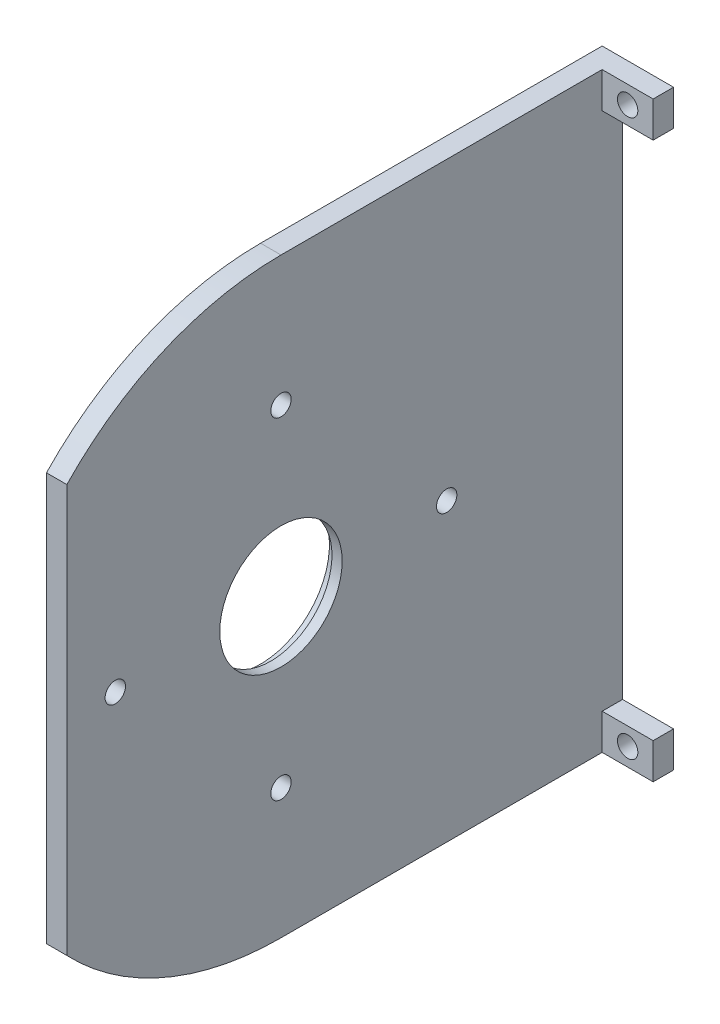
SolidWorks part; units mm, degrees
ref_plane "Front Plane" through (0, 0, 0) normal (0, 0, 1) x (1, 0, 0)
ref_plane "Top Plane" through (0, 0, 0) normal (0, 1, 0) x (1, 0, 0)
ref_plane "Right Plane" through (0, 0, 0) normal (1, 0, 0) x (0, 0, -1)
sketch "Sketch1" plane through (0, 0, 0) normal (1, 0, 0) x (0, 0, -1)
  line L0 (62.5, 58) -> (-4.5, 58)
  line L1 (-62.5, -58) -> (62.5, -58) construction
  line L2 (-62.5, -58) -> (-62.5, 58) construction
  line L3 (-62.5, 58) -> (62.5, 58) construction
  line L4 (62.5, -58) -> (62.5, 58) construction
  line L5 (-62.5, -58) -> (62.5, 58) construction
  line L6 (-62.5, 58) -> (62.5, -58) construction
  line L7 (62.5, -58) -> (-4.5, -58)
  line L8 (62.5, -58) -> (62.5, 58)
  arc A0 (-4.5, 58) -> (-4.5, -58) centre (-4.5, 0) ccw
  circle A2 centre (-4.5, 0) radius 12
  point P0 (0, 0)
  dimension "D3" = 116
  dimension "D4" = 24
  dimension "D1" = 125
  dimension "D2" = 116
extrude "Boss-Extrude1" add sketch "Sketch1" along normal blind 4
sketch "Sketch2" [suppressed] plane through (4, 0, 0) normal (1, 0, 0) x (0, 0, -1)
  circle A0 centre (-4.5, 0) radius 13.5
  circle A1 centre (-4.5, 0) radius 12 construction
  dimension "D1" = 27
extrude "Cut-Extrude1" [suppressed] cut sketch "Sketch2" against normal blind 2
sketch "Sketch4" plane through (0, 0, 0) normal (-1, 0, 0) x (0, 0, 1)
  circle A0 centre (4.5, 0) radius 13.5
  circle A1 centre (4.5, 0) radius 12 construction
  dimension "D1" = 27
extrude "Cut-Extrude2" cut sketch "Sketch4" against normal blind 2
sketch "Sketch5" [suppressed] plane through (0, 0, -62.5) normal (0, 0, -1) x (-1, 0, 0)
  line L0 (-4, -58) -> (-4, 58) construction
  line L1 (-4, 58) -> (-14, 58)
  line L2 (-4, 58) -> (-4, 51)
  line L3 (-4, 51) -> (-14, 51)
  line L4 (-14, 58) -> (-14, 51)
  line L5 (-4, 54.5) -> (-9, 54.5) construction
  line L6 (-4, 58) -> (0, 58) construction
  line L7 (0, 0) -> (12.1764, 0) construction
  line L8 (-4, -51) -> (-14, -51)
  line L9 (-14, -58) -> (-14, -51)
  line L10 (-4, -58) -> (-14, -58)
  line L11 (-4, -58) -> (-4, -51)
  line L12 (-2, 58) -> (-2, 71.3706) construction
  line L13 (0, -58) -> (0, -51)
  line L14 (0, -58) -> (10, -58)
  line L15 (10, -58) -> (10, -51)
  line L16 (0, -51) -> (10, -51)
  line L17 (0, 51) -> (10, 51) construction
  line L18 (10, 58) -> (10, 51) construction
  line L19 (0, 58) -> (10, 58) construction
  line L20 (0, 58) -> (0, 51) construction
  circle A0 centre (-9, 54.5) radius 2
  circle A1 centre (-9, -54.5) radius 2
  circle A2 centre (5, -54.5) radius 2
  circle A3 centre (5, 54.5) radius 2 construction
  dimension "D1" = 4
  dimension "D2" = 5
  dimension "D3" = 10
  dimension "D5" = 7
  dimension "D4" = 3.5
extrude "Boss-Extrude2" [suppressed] add sketch "Sketch5" against normal blind 4
sketch "Sketch6" plane through (0, 0, -62.5) normal (0, 0, -1) x (-1, 0, 0)
  line L0 (-4, -58) -> (-4, 58) construction
  line L1 (-4, 58) -> (-14, 58)
  line L2 (-4, 58) -> (-4, 51)
  line L3 (-4, 51) -> (-14, 51)
  line L4 (-14, 58) -> (-14, 51)
  line L5 (-4, 54.5) -> (-9, 54.5) construction
  line L6 (-2, -58) -> (-2, 0) construction
  line L7 (0, 0) -> (26.903, 0) construction
  line L8 (-4, -51) -> (-14, -51)
  line L9 (-14, -58) -> (-14, -51)
  line L10 (-4, -58) -> (-14, -58)
  line L11 (-4, -58) -> (-4, -51)
  line L12 (-4, 58) -> (0, 58) construction
  line L13 (-4, -58) -> (0, -58) construction
  line L14 (0, 51) -> (10, 51) construction
  line L15 (10, 58) -> (10, 51) construction
  line L16 (0, 58) -> (10, 58) construction
  line L17 (0, 58) -> (0, 51) construction
  line L18 (0, -58) -> (0, -51) construction
  line L19 (0, -58) -> (10, -58) construction
  line L20 (10, -58) -> (10, -51) construction
  line L21 (0, -51) -> (10, -51) construction
  circle A0 centre (-9, 54.5) radius 2
  circle A1 centre (-9, -54.5) radius 2
  circle A2 centre (5, -54.5) radius 2 construction
  circle A3 centre (5, 54.5) radius 2 construction
  dimension "D1" = 4
  dimension "D2" = 5
  dimension "D3" = 10
  dimension "D4" = 7
  dimension "D5" = 3.5
extrude "Boss-Extrude3" add sketch "Sketch6" against normal blind 4
sketch "Sketch7" [suppressed] plane through (0, 0, -62.5) normal (0, 0, -1) x (-1, 0, 0)
  line L0 (0, -58) -> (0, 58) construction
  line L1 (0, 58) -> (10, 58)
  line L2 (0, 58) -> (0, 51)
  line L3 (0, 51) -> (10, 51)
  line L4 (10, 58) -> (10, 51)
  line L5 (0, 0) -> (11.9371, 0) construction
  line L6 (0, -51) -> (10, -51)
  line L7 (10, -58) -> (10, -51)
  line L8 (0, -58) -> (10, -58)
  line L9 (0, -58) -> (0, -51)
  circle A0 centre (5, 54.5) radius 2
  circle A1 centre (5, -54.5) radius 2
  dimension "D5" = 3.5
  dimension "D3" = 4
  dimension "D1" = 10
  dimension "D2" = 7
  dimension "D4" = 5
extrude "Boss-Extrude4" [suppressed] add sketch "Sketch7" along normal blind 4 separate body
sketch "Sketch8" [suppressed] plane through (0, 0, 0) normal (-1, 0, 0) x (0, 0, 1)
  circle A0 centre (4.5, 0) radius 20
  dimension "D1" = 40
extrude "Cut-Extrude3" [suppressed] cut sketch "Sketch8" against normal through all
sketch "Sketch9" plane through (4, 0, 0) normal (1, 0, 0) x (0, 0, -1)
  line L0 (-46.5, 40) -> (-46.5, -40)
  arc A0 (-4.5, 58) -> (-4.5, -58) centre (-4.5, 0) ccw construction
  arc A1 (-46.5, 40) -> (-46.5, -40) centre (-4.5, 0) ccw
  dimension "D1" = 80
extrude "Cut-Extrude4" cut sketch "Sketch9" against normal through all
sketch "Sketch10" [suppressed] plane through (0, 0, 0) normal (-1, 0, 0) x (0, 0, 1)
  circle A0 centre (4.5, 0) radius 27.5
  dimension "D1" = 55
extrude "Cut-Extrude5" [suppressed] cut sketch "Sketch10" against normal through all
sketch "Sketch11" [suppressed] plane through (0, 0, 0) normal (-1, 0, 0) x (0, 0, 1)
  circle A0 centre (4.5, 0) radius 29
  dimension "D1" = 58
extrude "Cut-Extrude6" [suppressed] cut sketch "Sketch11" against normal blind 2
sketch "Sketch12" [suppressed] plane through (0, 0, 0) normal (-1, 0, 0) x (0, 0, 1)
  circle A0 centre (4.5, 0) radius 32.5 construction
  circle A1 centre (4.5, 32.5) radius 2
  circle A2 centre (37, 0) radius 2
  circle A3 centre (4.5, -32.5) radius 2
  circle A4 centre (-28, 0) radius 2
  point P14 (4.5, 0)
  dimension "D1" = 65
  dimension "D2" = 4
  dimension "D3" = 4
extrude "Cut-Extrude7" [suppressed] cut sketch "Sketch12" against normal through all
sketch "Sketch13" plane through (0, 0, 0) normal (-1, 0, 0) x (0, 0, 1)
  circle A0 centre (4.5, 0) radius 32.5 construction
  circle A1 centre (4.5, 32.5) radius 2
  circle A2 centre (37, 0) radius 2
  circle A3 centre (4.5, -32.5) radius 2
  circle A4 centre (-28, 0) radius 2
  point P6 (-20.098, 11.856)
  point P7 (4.5, 0)
  point P13 (4.5, 0)
  dimension "D1" = 65
  dimension "D2" = 4
  dimension "D3" = 4
extrude "Cut-Extrude8" cut sketch "Sketch13" against normal through all
equation "\"D4@Sketch5\"=\"D5@Sketch5\"/2"
equation "\"D5@Sketch6\"=\"D4@Sketch6\"/2"
equation "\"D5@Sketch7\"=\"D2@Sketch7\"/2"
